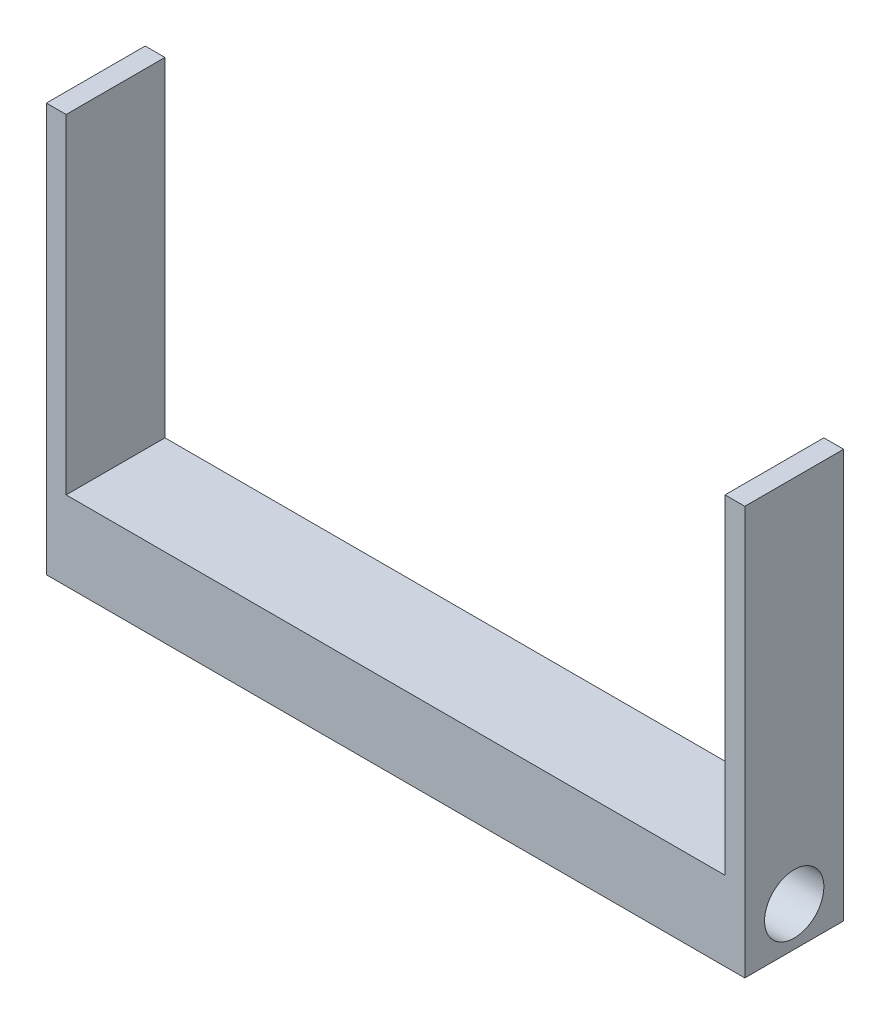
SolidWorks part; units mm, degrees
material "PLA"
ref_plane "Front Plane" through (0, 0, 0) normal (0, 0, 1) x (1, 0, 0)
ref_plane "Top Plane" through (0, 0, 0) normal (0, 1, 0) x (1, 0, 0)
ref_plane "Right Plane" through (0, 0, 0) normal (1, 0, 0) x (0, 0, -1)
sketch "Sketch1" plane through (0, 0, 0) normal (0, 0, 1) x (1, 0, 0)
  line L0 (-50, 0) -> (-50, -50)
  line L1 (-50, -50) -> (50, -50)
  line L2 (50, -50) -> (50, 0)
  dimension "D1" = 50
  dimension "D2" = 100
  dimension "D3" = 50
  dimension "D4" = 50
extrude "Extrude-Thin1" add sketch "Sketch1" along normal mid plane 15 thin thin type one direction wall 3
sketch "Sketch4" plane through (0, -53, 0) normal (0, -1, 0) x (1, 0, 0)
  line L4 (-53, -7.5) -> (53, -7.5)
  line L5 (53, -7.5) -> (53, 7.5)
  line L6 (53, 7.5) -> (-53, 7.5)
  line L7 (-53, 7.5) -> (-53, -7.5)
  line L8 (-53, -7.5) -> (53, -7.5)
  line L9 (53, -7.5) -> (53, 7.5)
  line L10 (53, 7.5) -> (-53, 7.5)
  line L11 (-53, 7.5) -> (-53, -7.5)
  dimension "D1" = 0
extrude "Boss-Extrude1" add sketch "Sketch4" along normal blind 9
sketch "Sketch5" plane through (53, 0, 0) normal (1, 0, 0) x (0, 0, -1)
  line L0 (7.5, -62) -> (-7.5, -62) construction
  line L1 (-7.5, -62) -> (-7.5, 0) construction
  circle A0 centre (0, -56) radius 4.5
  dimension "D1" = 9
  dimension "D2" = 6
  dimension "D3" = 7.5
extrude "Cut-Extrude1" cut sketch "Sketch5" against normal through all
